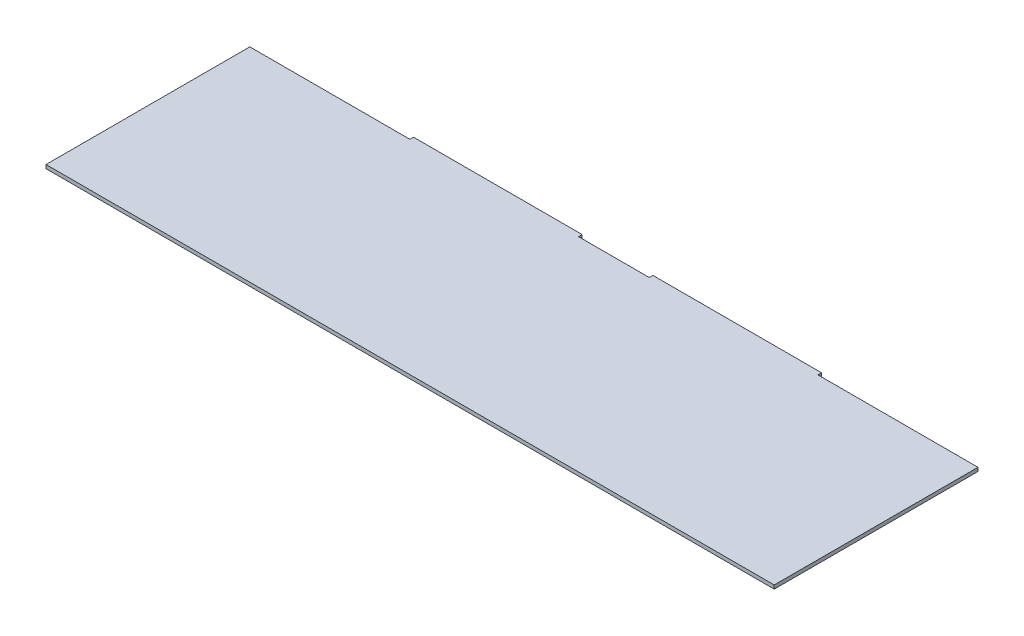
SolidWorks part; units mm, degrees
material "6061-T6 (SS)"
ref_plane "X-Y Datum" through (0, 0, 0) normal (0, 0, 1) x (1, 0, 0)
ref_plane "X-Z Datum" through (0, 0, 0) normal (0, 1, 0) x (1, 0, 0)
ref_plane "Y-Z Datum" through (0, 0, 0) normal (1, 0, 0) x (0, 0, -1)
sketch "Sketch1" plane through (0, 0, 0) normal (0, 1, 0) x (1, 0, 0)
  line L1 (-317.6778, 88.9) -> (317.6778, 88.9)
  line L2 (-317.6778, 88.9) -> (-317.6778, -88.9)
  line L3 (-317.6778, -88.9) -> (317.6778, -88.9)
  line L4 (317.6778, 88.9) -> (317.6778, -88.9)
  line L5 (-317.6778, 88.9) -> (317.6778, -88.9) construction
  line L6 (-317.6778, -88.9) -> (317.6778, 88.9) construction
  point P0 (0, 0)
  dimension "D1" = 635.3556
  dimension "D2" = 177.8
extrude "Boss-Extrude1" add sketch "Sketch1" along normal mid plane 3.175
sketch "Sketch2" plane through (0, 0, -88.9) normal (0, 0, -1) x (-1, 0, 0)
  line L1 (177.9778, -1.5875) -> (177.9778, 1.5875)
  line L2 (-177.9778, -1.5875) -> (-177.9778, 1.5875)
  line L20 (-317.6778, -1.5875) -> (317.6778, -1.5875) construction
  line L21 (-177.9778, -1.5875) -> (-30.8229, -1.5875)
  line L22 (30.8229, -1.5875) -> (177.9778, -1.5875)
  line L40 (30.8229, -1.5875) -> (30.8229, 1.5875)
  line L41 (30.8229, 1.5875) -> (177.9778, 1.5875)
  line L57 (-177.9778, 1.5875) -> (-30.8229, 1.5875)
  line L58 (-30.8229, 1.5875) -> (-30.8229, -1.5875)
extrude "Boss-Extrude2" add sketch "Sketch2" along normal blind 3.175
